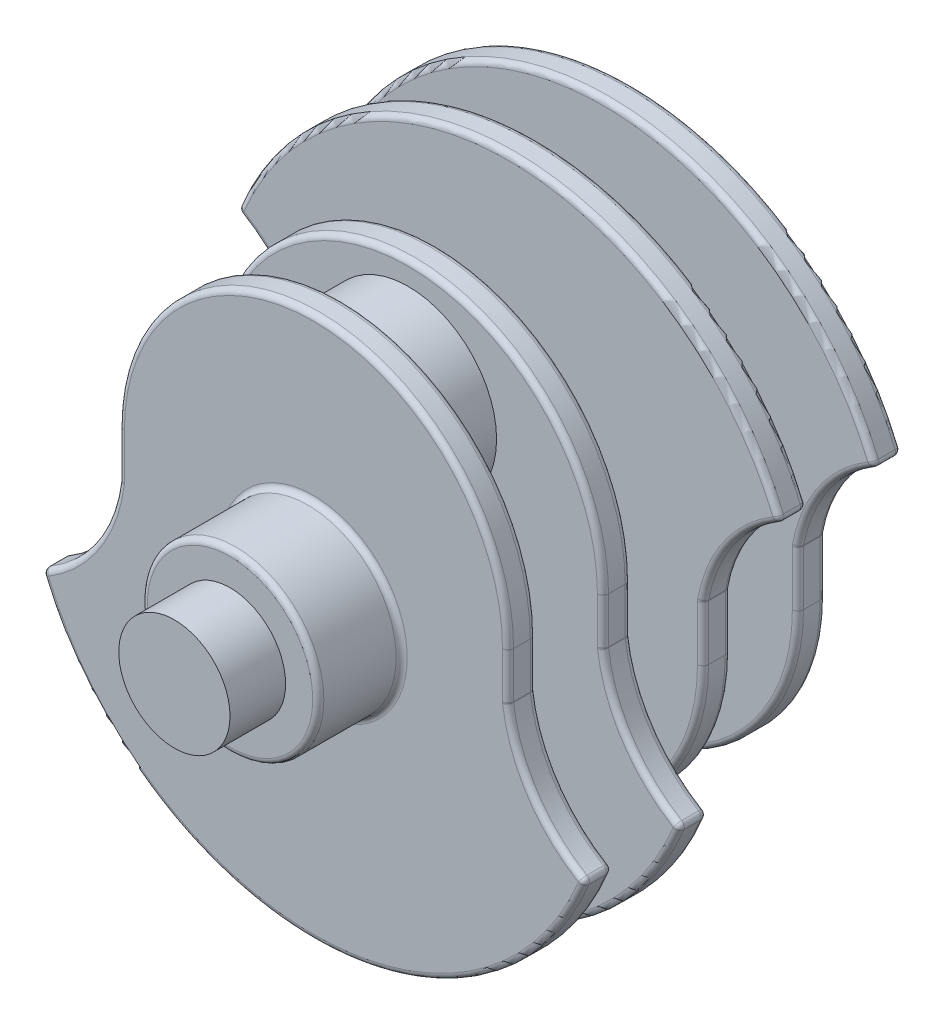
SolidWorks part; units mm, degrees
material "AISI 4340 Steel, normalized"
ref_plane "Front Plane" through (0, 0, 0) normal (0, 0, 1) x (1, 0, 0)
ref_plane "Top Plane" through (0, 0, 0) normal (0, 1, 0) x (1, 0, 0)
ref_plane "Right Plane" through (0, 0, 0) normal (1, 0, 0) x (0, 0, -1)
sketch "Sketch1" plane through (0, 0, 0) normal (0, 0, 1) x (1, 0, 0)
  circle A0 centre (0, 0) radius 31.75
  dimension "D1" = 31.75
extrude "Boss-Extrude1" add sketch "Sketch1" along normal blind 30
sketch "Sketch8" plane through (0, 0, 0) normal (0, 0, -1) x (-1, 0, 0)
  line L0 (-70, 20) -> (-70, 3.36)
  line L1 (70, 20) -> (70, 3.36)
  arc A0 (70, 20) -> (-70, 20) centre (0, 20) ccw
  arc A5 (-97.7839, -38.2532) -> (97.7839, -38.2532) centre (0, 0) ccw
  arc A6 (-70, 3.36) -> (-97.7839, -38.2532) centre (-125, 10) cw
  arc A7 (70, 3.36) -> (97.7839, -38.2532) centre (125, 10) ccw
  dimension "D1" = 70
  dimension "D2" = 105
  dimension "D3" = 20
  dimension "D5" = 10
  dimension "D6" = 125
extrude "Boss-Extrude5" add sketch "Sketch8" along normal blind 10
sketch "Sketch2" plane through (0, 0, 30) normal (0, 0, 1) x (1, 0, 0)
  circle A0 centre (0, 0) radius 20
  dimension "D1" = 20
extrude "Boss-Extrude2" add sketch "Sketch2" along normal blind 20
sketch "Sketch9" plane through (0, 0, -10) normal (0, 0, -1) x (-1, 0, 0)
  circle A0 centre (0, 50) radius 31.75
  dimension "D2" = 31.75
  dimension "D1" = 50
extrude "Boss-Extrude6" add sketch "Sketch9" along normal blind 24.13
ref_plane "Plane4" through (0, 0, -70.13) normal (0, 0, -1) x (-1, 0, 0)
sketch "Sketch10" plane through (0, 0, -34.13) normal (0, 0, -1) x (-1, 0, 0)
  line L0 (-70, -20) -> (-70, 0)
  line L1 (70, -20) -> (70, 0)
  arc A0 (-70, -20) -> (70, -20) centre (0, -20) ccw
  arc A1 (-70, 0) -> (-97.598, 38.7251) centre (-125, -10) ccw
  arc A2 (70, 0) -> (97.598, 38.7251) centre (125, -10) cw
  arc A3 (-97.598, 38.7251) -> (97.598, 38.7251) centre (0, 0) cw
  dimension "D1" = 70
  dimension "D3" = 105
  dimension "D2" = 20
  dimension "D4" = 125
  dimension "D5" = 10
extrude "Boss-Extrude7" add sketch "Sketch10" along normal blind 10 from surface starting at plane "Plane4"
ref_plane "Plane3" through (0, 0, -104.26) normal (0, 0, -1) x (-1, 0, 0)
sketch "Sketch12" plane through (0, 0, -104.26) normal (0, 0, -1) x (-1, 0, 0)
  line L2 (70, -20) -> (70, 0)
  line L3 (70, -20) -> (70, 0)
  line L4 (-70, 0) -> (-70, -20)
  line L5 (-70, 0) -> (-70, -20)
  arc A12 (-70, -20) -> (70, -20) centre (0, -20) ccw
  arc A13 (97.598, 38.7251) -> (70, 0) centre (125, -10) ccw
  arc A14 (97.598, 38.7251) -> (-97.598, 38.7251) centre (0, 0) ccw
  arc A15 (-70, 0) -> (-97.598, 38.7251) centre (-125, -10) ccw
  arc A16 (-70, -20) -> (70, -20) centre (0, -20) ccw
  arc A17 (97.598, 38.7251) -> (70, 0) centre (125, -10) ccw
  arc A18 (97.598, 38.7251) -> (-97.598, 38.7251) centre (0, 0) ccw
  arc A19 (-70, 0) -> (-97.598, 38.7251) centre (-125, -10) ccw
  dimension "D1" = 0
extrude "Boss-Extrude8" add sketch "Sketch12" along normal blind 10
sketch "Sketch14" plane through (0, 0, -80.13) normal (0, 0, -1) x (-1, 0, 0)
  circle A0 centre (0, -50) radius 31.75
  dimension "D2" = 31.75
  dimension "D1" = 50
extrude "Boss-Extrude9" add sketch "Sketch14" along normal up to next
sketch "Sketch15" plane through (0, 0, -114.26) normal (0, 0, -1) x (-1, 0, 0)
  circle A1 centre (0, 0) radius 31.75
  circle A2 centre (0, 0) radius 31.75
  dimension "D1" = 0
extrude "Boss-Extrude10" add sketch "Sketch15" along normal blind 30
sketch "Sketch16" plane through (0, 0, -144.26) normal (0, 0, -1) x (-1, 0, 0)
  circle A1 centre (0, 0) radius 20
  circle A2 centre (0, 0) radius 20
  dimension "D1" = 0
extrude "Boss-Extrude11" add sketch "Sketch16" along normal blind 20
sketch "Sketch18" plane through (0, 0, -34.13) normal (0, 0, -1) x (-1, 0, 0)
  line L2 (-70, 20) -> (-70, 3.36)
  line L3 (-70, 20) -> (-70, 3.36)
  line L4 (70, 3.36) -> (70, 20)
  line L5 (70, 3.36) -> (70, 20)
  arc A4 (70, 20) -> (-70, 20) centre (0, 20) ccw
  arc A5 (-97.7839, -38.2532) -> (-70, 3.36) centre (-125, 10) ccw
  arc A6 (-97.7839, -38.2532) -> (97.7839, -38.2532) centre (0, 0) ccw
  arc A7 (70, 3.36) -> (97.7839, -38.2532) centre (125, 10) ccw
  arc A8 (70, 20) -> (-70, 20) centre (0, 20) ccw
  arc A9 (-97.7839, -38.2532) -> (-70, 3.36) centre (-125, 10) ccw
  arc A10 (-97.7839, -38.2532) -> (97.7839, -38.2532) centre (0, 0) ccw
  arc A11 (70, 3.36) -> (97.7839, -38.2532) centre (125, 10) ccw
  dimension "D1" = 0
extrude "Boss-Extrude12" add sketch "Sketch18" along normal blind 10
sketch "Sketch19" plane through (0, 0, -44.13) normal (0, 0, -1) x (-1, 0, 0)
  circle A1 centre (0, 0) radius 31.75
  circle A2 centre (0, 0) radius 31.75
  dimension "D1" = 0
extrude "Boss-Extrude13" add sketch "Sketch19" along normal up to next
fillet "Fillet1" radius 2 32 edges at (0, -105, -34.13) (-78.9263, -20.762, -34.13) (-70, 11.68, -34.13) (70, 11.68, -34.13) (78.9263, -20.762, -34.13) (0, -105, -44.13) (-78.9263, -20.762, -44.13) (-70, 11.68, -44.13) (0, 90, -44.13) (70, 11.68, -44.13) (78.9263, -20.762, -44.13) (97.7839, -38.2532, -39.13) (70, 3.36, -39.13) (-70, 3.36, -39.13) (-97.7839, -38.2532, -39.13) (0, 90, -34.13) (70, 11.68, 0) (78.9263, -20.762, 0) (0, -105, 0) (-78.9263, -20.762, 0) (-70, 11.68, 0) (0, 90, -10) (70, 11.68, -10) (78.9263, -20.762, -10) (0, -105, -10) (-78.9263, -20.762, -10) (-70, 11.68, -10) (-70, 3.36, -5) (-97.7839, -38.2532, -5) (97.7839, -38.2532, -5) (70, 3.36, -5) (0, 90, 0)
fillet "Fillet2" radius 2 16 edges at (0, 105, -104.26) (79.4761, 22.4433, -104.26) (70, -10, -104.26) (0, -90, -104.26) (-70, -10, -104.26) (-79.4761, 22.4433, -104.26) (79.4761, 22.4433, -114.26) (70, -10, -114.26) (0, -90, -114.26) (-70, -10, -114.26) (-79.4761, 22.4433, -114.26) (-97.598, 38.7251, -109.26) (-70, 0, -109.26) (70, 0, -109.26) (97.598, 38.7251, -109.26) (0, 105, -114.26)
fillet "Fillet3" radius 2 16 edges at (70, -10, -70.13) (79.4761, 22.4433, -70.13) (0, 105, -70.13) (-79.4761, 22.4433, -70.13) (-70, -10, -70.13) (0, -90, -70.13) (70, -10, -80.13) (79.4761, 22.4433, -80.13) (-79.4761, 22.4433, -80.13) (-70, -10, -80.13) (0, -90, -80.13) (70, 0, -75.13) (97.598, 38.7251, -75.13) (-97.598, 38.7251, -75.13) (-70, 0, -75.13) (0, 105, -80.13)
fillet "Fillet5" radius 2 2 edges at (31.75, 0, 30) (31.75, 0, 0)
fillet "Fillet6" radius 2 2 edges at (-31.75, 0, -114.26) (-31.75, 0, -144.26)
fillet "Fillet9" radius 2 2 edges at (-31.75, -50, -80.13) (-31.75, -50, -104.26)
equation "\"Crank Radius\"= 50mm"
equation "\"D1@Sketch9\"=\"Crank Radius\""
equation "\"D1@Sketch14\"=\"Crank Radius\""
